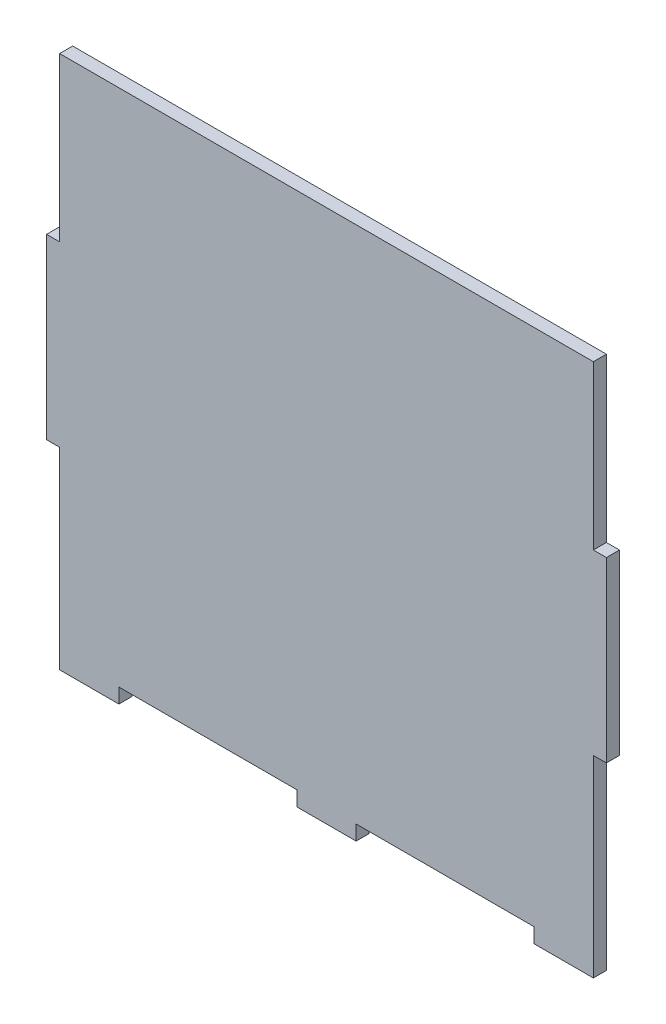
SolidWorks part; units mm, degrees
ref_plane "Front Plane" through (0, 0, 0) normal (0, 0, 1) x (1, 0, 0)
ref_plane "Top Plane" through (0, 0, 0) normal (0, 1, 0) x (1, 0, 0)
ref_plane "Right Plane" through (0, 0, 0) normal (1, 0, 0) x (0, 0, -1)
sketch "Sketch1" plane through (0, 0, 0) normal (0, 0, 1) x (1, 0, 0)
  line L0 (4.191, 181.2388) -> (4.191, -47.3862) construction
  line L1 (-110.109, 181.2388) -> (118.491, 181.2388)
  line L2 (-110.109, 181.2388) -> (-110.109, -47.3612)
  line L3 (-110.109, -47.3612) -> (-84.709, -47.3612)
  line L4 (118.491, 181.2388) -> (118.491, -47.3612)
  line L5 (-110.109, 66.9388) -> (118.491, 66.9388) construction
  line L6 (124.079, 35.1888) -> (118.491, 35.1888)
  line L7 (-115.697, 111.3888) -> (-110.109, 111.3888)
  line L8 (-115.697, 111.3888) -> (-115.697, 35.1888)
  line L9 (-115.697, 35.1888) -> (-110.109, 35.1888)
  line L11 (-8.509, -47.3862) -> (4.191, -47.3862)
  line L12 (93.091, -47.3612) -> (93.091, -41.0362)
  line L13 (-84.709, -47.3612) -> (-84.709, -41.0362)
  line L14 (-84.709, -41.0362) -> (-8.509, -41.0362)
  line L15 (124.079, 111.3888) -> (124.079, 35.1888)
  line L16 (124.079, 111.3888) -> (118.491, 111.3888)
  line L23 (-8.509, -47.3862) -> (-8.509, -41.0362)
  line L24 (93.091, -41.0362) -> (16.891, -41.0362)
  line L25 (16.891, -47.3862) -> (16.891, -41.0362)
  line L26 (16.891, -47.3862) -> (4.191, -47.3862)
  line L27 (118.491, -47.3612) -> (93.091, -47.3612)
  point P29 (-84.709, -44.1987)
  dimension "D1" = 228.6
  dimension "D2" = 228.6
  dimension "D3" = 5.588
  dimension "D4" = 76.2
  dimension "D6" = 25.4
  dimension "D5" = 82.55
extrude "Boss-Extrude1" add sketch "Sketch1" along normal blind 5.588 contours L27 L4 L1 L2 L3 L13 L14 L23 L11 L26 L25 L24 L12 | L8 L9 L2 L7 | L15 L16 L4 L6 region at (4.191, 69.0259, 0) region at (-112.903, 73.2888, 0) region at (121.285, 73.2888, 0)
equation "\"width\"= 9in"
equation "\"Height\"= 18in"
equation "\"thick\"= 0.22"
equation "\"D1@Sketch1\"=\"width\""
equation "\"D2@Sketch1\"=\"width\""
equation "\"D3@Sketch1\"=\"thick\""
equation "\"D1@Boss-Extrude1\"=\"thick\""
